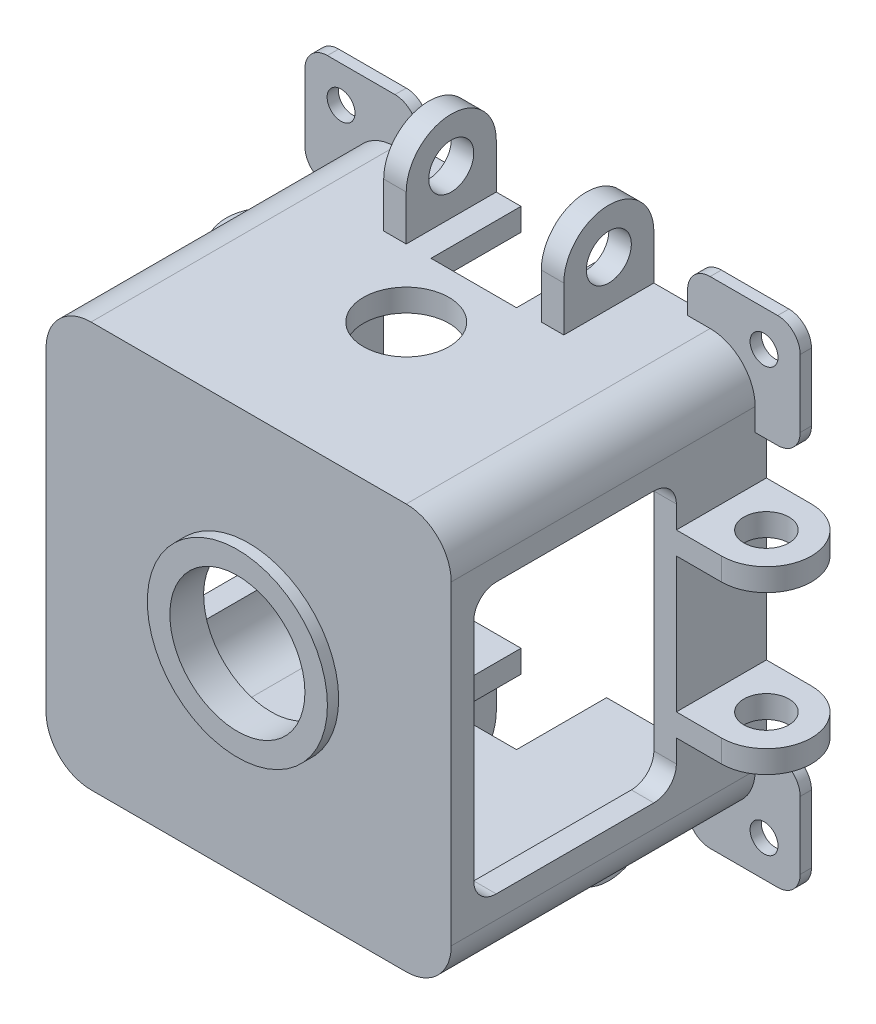
SolidWorks part; units mm, degrees
other "标注1"
sketch "草图6" plane through (67.5, -67.5, 0) normal (0.0299, -0.9992, -0.0283) x (0.0877, 0.0308, -0.9957)
material "2024 合金"
ref_plane "前视基准面" through (0, 0, 0) normal (0, 0, 1) x (1, 0, 0)
ref_plane "上视基准面" through (0, 0, 0) normal (0, 1, 0) x (1, 0, 0)
ref_plane "右视基准面" through (0, 0, 0) normal (1, 0, 0) x (0, 0, -1)
sketch "草图1" plane through (0, 0, 0) normal (0, 0, 1) x (1, 0, 0)
  line L1 (-35, -45) -> (35, -45)
  line L2 (-45, -35) -> (-45, 35)
  line L3 (-35, 45) -> (35, 45)
  line L4 (45, -35) -> (45, 35)
  line L5 (-45, -45) -> (45, 45) construction
  line L6 (-45, 45) -> (45, -45) construction
  line L7 (-30, -40) -> (30, -40)
  line L8 (-40, -30) -> (-40, 30)
  line L9 (-30, 40) -> (30, 40)
  line L10 (40, -30) -> (40, 30)
  line L11 (-40, -40) -> (40, 40) construction
  line L12 (-40, 40) -> (40, -40) construction
  arc A0 (35, -45) -> (45, -35) centre (35, -35) ccw
  arc A1 (30, -40) -> (40, -30) centre (30, -30) ccw
  arc A2 (-35, -45) -> (-45, -35) centre (-35, -35) cw
  arc A3 (-30, -40) -> (-40, -30) centre (-30, -30) cw
  arc A4 (-45, 35) -> (-35, 45) centre (-35, 35) cw
  arc A5 (35, 45) -> (45, 35) centre (35, 35) cw
  arc A6 (30, 40) -> (40, 30) centre (30, 30) cw
  arc A7 (-40, 30) -> (-30, 40) centre (-30, 30) cw
  point P0 (0, 0)
  point P7 (0, 0)
  dimension "D1" = 90
  dimension "D5" = 10
  dimension "D2" = 90
  dimension "D3" = 80
  dimension "D4" = 80
extrude "凸台-拉伸1" add sketch "草图1" along normal blind 70
sketch "草图3" plane through (0, 45, 0) normal (0, 1, 0) x (1, 0, 0)
  line L0 (0, 0) -> (0, -35) construction
  line L1 (35, 0) -> (-35, 0) construction
  line L2 (35, 0) -> (-35, 0) construction
  line L3 (9.5, 20) -> (-9.5, 20)
  line L4 (9.5, 20) -> (9.5, -20)
  line L5 (9.5, -20) -> (-9.5, -20)
  line L6 (-9.5, 20) -> (-9.5, -20)
  line L7 (9.5, 20) -> (-9.5, -20) construction
  line L8 (9.5, -20) -> (-9.5, 20) construction
  circle A0 centre (0, -35) radius 9.5
  dimension "D2" = 19
  dimension "D1" = 35
  dimension "D3" = 20
  dimension "D4" = 19
extrude "切除-拉伸2" cut sketch "草图3" against normal through all
sketch "草图4" plane through (0, -1.9977, 89.2652) normal (1, 0, 0) x (0, 0, -1)
  line L0 (69.2652, -42.0023) -> (69.2652, -53.0023)
  line L3 (89.2652, -53.0023) -> (89.2652, -42.0023)
  line L5 (89.2652, -42.0023) -> (69.2652, -42.0023)
  arc A0 (69.2652, -53.0023) -> (89.2652, -53.0023) centre (79.2652, -53.0023) ccw
  circle A1 centre (79.2652, -53.0023) radius 5
  dimension "D3" = 10
  dimension "D1" = 11
extrude "凸台-拉伸2" add sketch "草图4" along normal blind 20 and the other way blind 20
sketch "草图5" plane through (0, 0, 0) normal (0, 0, -1) x (-1, 0, 0)
  line L0 (0, 0) -> (0, -60.5) construction
  line L1 (15, -45) -> (-15, -45)
  line L2 (15, -45) -> (15, -76)
  line L3 (15, -76) -> (-15, -76)
  line L4 (-15, -45) -> (-15, -76)
  line L5 (15, -45) -> (-15, -76) construction
  line L6 (15, -76) -> (-15, -45) construction
  line L9 (-20, -45) -> (-35, -45) construction
  point P0 (0, -60.5)
  dimension "D1" = 30
  dimension "D2" = 31
extrude "切除-拉伸3" cut sketch "草图5" against normal up to surface (20 mm away) up to face at (0, -50, 20)
sketch "草图17" plane through (0, -44, 0) normal (0, 1, 0) x (1, 0, 0)
  line L1 (-9.5, -20) -> (9.5, -20)
  line L2 (-9.5, -20) -> (-9.5, 0)
  line L3 (-9.5, 0) -> (9.5, 0)
  line L4 (9.5, -20) -> (9.5, 0)
extrude "切除-拉伸7" cut sketch "草图17" against normal through all and the other way through all
ref_plane "基准面1" through (0, 0, 0) normal (0, -1, 0) x (-1, 0, 0)
ref_plane "基准面2" through (0, 0, 0) normal (1, 0, 0) x (0, 0, -1)
ref_axis "基准轴1" through (0, 0, 26.25) along (0, 0, -1)
pattern_circular "阵列(圆周)3" count 4 over 360 about axis through (0, 0, 26.25) along (0, 0, -1) of "切除-拉伸3", "凸台-拉伸2"
sketch "草图13" plane through (0, 0, 70) normal (0, 0, 1) x (1, 0, 0)
  line L1 (40, 40) -> (-40, 40)
  line L2 (40, 40) -> (40, -40)
  line L3 (40, -40) -> (-40, -40)
  line L4 (-40, 40) -> (-40, -40)
  line L5 (40, 40) -> (-40, -40) construction
  line L6 (40, -40) -> (-40, 40) construction
  circle A0 centre (0, 0) radius 15
  point P0 (0, 0)
  dimension "D3" = 30
  dimension "D1" = 80
  dimension "D2" = 80
extrude "凸台-拉伸3" add sketch "草图13" against normal blind 5
sketch "草图14" plane through (0, 0, 70) normal (0, 0, 1) x (1, 0, 0)
  circle A0 centre (0, 0) radius 15
  circle A1 centre (0, 0) radius 20
  dimension "D1" = 30
  dimension "D2" = 40
extrude "凸台-拉伸4" add sketch "草图14" along normal blind 2.5 and the other way blind 7.5
sketch "草图15" plane through (0, 0, 0) normal (0, 0, -1) x (-1, 0, 0)
  line L0 (-50, 50) -> (-30, 30) construction
  line L1 (-40, -30) -> (-40, 30) construction
  line L3 (-30, 40) -> (-9.5, 40) construction
  line L4 (-40, 30) -> (-50, 30)
  line L5 (-30, 40) -> (-30, 50)
  line L6 (-35, 55) -> (-50, 55)
  line L7 (-55, 35) -> (-55, 50)
  arc A0 (-30, 40) -> (-40, 30) centre (-30, 30) ccw construction
  arc A1 (-40, 30) -> (-30, 40) centre (-30, 30) cw
  arc A2 (-50, 55) -> (-55, 50) centre (-50, 50) ccw
  arc A3 (-30, 50) -> (-35, 55) centre (-35, 50) ccw
  arc A4 (-50, 30) -> (-55, 35) centre (-50, 35) cw
  circle A6 centre (-46.9706, 46.9706) radius 3.1
  point P17 (-55, 55)
  point P20 (-30, 55)
  point P23 (-55, 30)
  dimension "D3" = 5
  dimension "D4" = 6.2
  dimension "D1" = 25
  dimension "D2" = 25
  dimension "D5" = 24
extrude "凸台-拉伸5" add sketch "草图15" against normal blind 2.5
mirror "镜向2" about plane through (0, 0, 0) normal (1, 0, 0) of "凸台-拉伸5"
mirror "镜向3" about plane through (0, 0, 0) normal (0, -1, 0) of "镜向2"
sketch "草图16" plane through (-45, 0, 0) normal (-1, 0, 0) x (0, 0, 1)
  line L0 (20, -15) -> (20, -20) construction
  line L1 (25, 30) -> (60, 30)
  line L2 (20, 25) -> (20, -25)
  line L3 (25, -30) -> (60, -30)
  line L4 (65, 25) -> (65, -25)
  line L5 (20, 30) -> (65, -30) construction
  line L6 (20, -30) -> (65, 30) construction
  line L7 (70, 35) -> (70, -35) construction
  line L8 (0, 0) -> (42.5, 0) construction
  arc A0 (60, 30) -> (65, 25) centre (60, 25) cw
  arc A1 (25, 30) -> (20, 25) centre (25, 25) ccw
  arc A2 (20, -25) -> (25, -30) centre (25, -25) ccw
  arc A3 (60, -30) -> (65, -25) centre (60, -25) ccw
  point P0 (42.5, 0)
  dimension "D3" = 5
  dimension "D1" = 5
  dimension "D2" = 60
extrude "切除-拉伸6" cut sketch "草图16" against normal through all
sketch "草图18" plane through (0, 44, 0) normal (0, -1, 0) x (1, 0, 0)
  line L1 (9.5, 20) -> (-9.5, 20)
  line L2 (9.5, 20) -> (9.5, 0)
  line L3 (9.5, 0) -> (-9.5, 0)
  line L4 (-9.5, 20) -> (-9.5, 0)
extrude "切除-拉伸8" cut sketch "草图18" against normal through all
